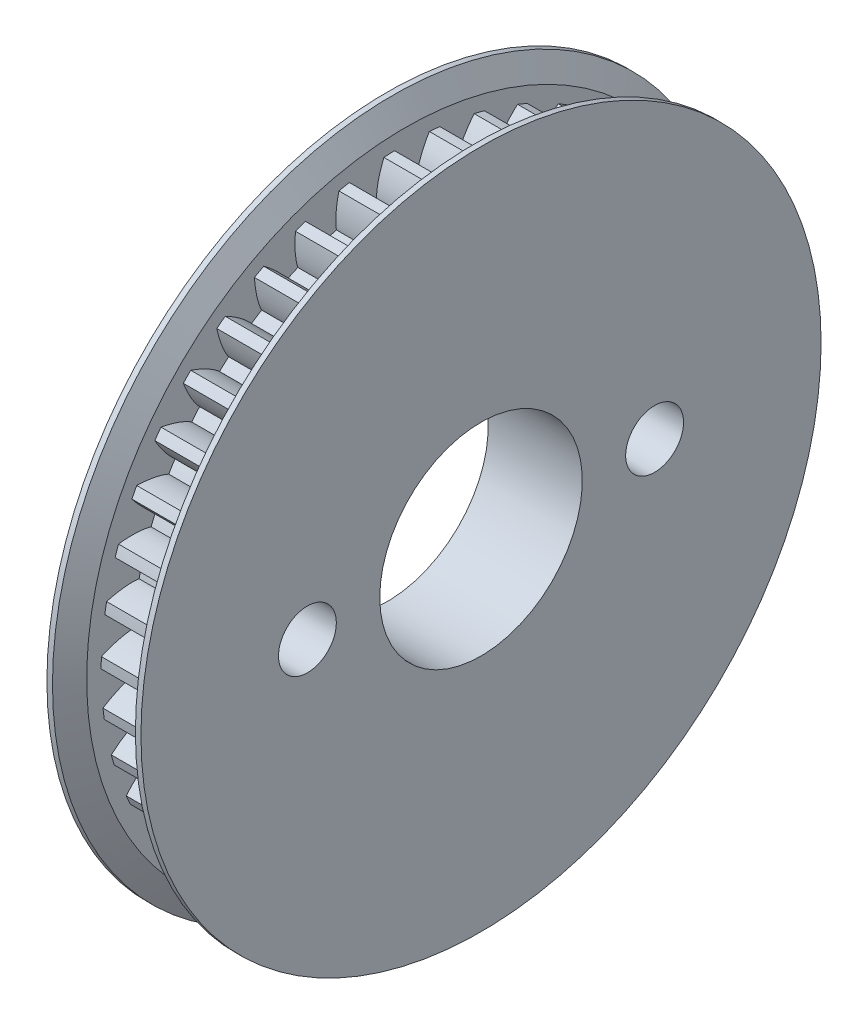
SolidWorks part; units mm, degrees
material "6061-T6 (SS)"
ref_plane "Front Plane" through (0, 0, 0) normal (1, 0, 0) x (0, 1, 0)
ref_plane "Top Plane" through (0, 0, 0) normal (0, 0, 1) x (0, 1, 0)
ref_plane "Right Plane" through (0, 0, 0) normal (0, 1, 0) x (-1, 0, 0)
sketch "Sketch1" plane through (0, 0, 0) normal (1, 0, 0) x (0, 1, 0)
  circle A0 centre (0, 0) radius 21.0085
  circle A1 centre (0, 0) radius 18.8441 construction
  circle A2 centre (0, 0) radius 18.8599 construction
  circle A3 centre (0, 0) radius 20.0535 construction
  dimension "D1" = 42.0169
  dimension "D2" = 37.6883
  dimension "D3" = 37.7197
  dimension "D4" = 40.107
extrude "Boss-Extrude1" add sketch "Sketch1" along normal blind 4
sketch "Sketch3" plane through (4, 0, 0) normal (1, 0, 0) x (0, 1, 0)
  line L0 (0, 0) -> (18.8441, 0) construction
  line L1 (0, 0) -> (20.0513, 0.2989) construction
  line L2 (0, 0) -> (20.0484, -0.4511) construction
  line L3 (20.0484, -0.4511) -> (18.8394, -0.4239)
  line L4 (20.0484, -0.4511) -> (26.0383, -0.5858)
  line L5 (26.0383, 5.6753) -> (26.0383, -0.5858)
  line L6 (18.8441, 0) -> (18.8599, 0)
  line L7 (18.8394, -0.4239) -> (18.8551, -0.4242)
  circle A0 centre (0, 0) radius 20.0535 construction
  circle A1 centre (0, 0) radius 18.8441 construction
  circle A2 centre (0, 0) radius 18.8599 construction
  arc A3 (18.8599, 0) -> (18.8551, -0.4242) centre (0, 0) cw
  spline S0 degree 4 poles (18.8441, 0) (18.8581, 0.0003) (18.8971, 0.002) (18.9708, 0.0089) (19.0905, 0.0253) (19.242, 0.0535) (19.4365, 0.0986) (19.6634, 0.1625) (19.9101, 0.2441) (20.175, 0.3448) (20.436, 0.456) (20.6929, 0.5763) (20.9457, 0.7052) (21.2473, 0.8707) (21.6037, 1.0842) (22.0093, 1.3516) (22.4593, 1.681) (22.901, 2.0358) (23.3282, 2.4114) (23.7378, 2.8006) (24.1355, 3.2108) (24.5122, 3.6264) (24.8835, 4.0701) (25.1799, 4.4449) (25.4486, 4.8104) (25.6694, 5.1179) (25.9451, 5.5285) (26.1166, 5.7943) (26.3702, 6.2065) (26.4595, 6.3635) (26.5307, 6.485) knots 0 0 0 0 0 0.005377 0.015084 0.028532 0.04661 0.064855 0.092111 0.119476 0.146842 0.174209 0.201575 0.228941 0.256307 0.307035 0.361767 0.4165 0.471232 0.525964 0.580697 0.635429 0.690161 0.744894 0.799626 0.826992 0.854358 0.909091 0.954545 1 1 1 1 1 construction
  spline S1 degree 4 poles (18.8441, 0) (18.8581, 0.0003) (18.8971, 0.002) (18.9708, 0.0089) (19.0905, 0.0253) (19.242, 0.0535) (19.4365, 0.0986) (19.6634, 0.1625) (19.9101, 0.2441) (20.175, 0.3448) (20.436, 0.456) (20.6929, 0.5763) (20.9457, 0.7052) (21.2473, 0.8707) (21.6037, 1.0842) (22.0093, 1.3516) (22.4593, 1.681) (22.901, 2.0358) (23.3282, 2.4114) (23.7378, 2.8006) (24.1355, 3.2108) (24.5122, 3.6264) (24.8835, 4.0701) (25.1799, 4.4449) (25.4486, 4.8104) (25.6694, 5.1179) (25.8642, 5.4081) (25.9687, 5.5668) (26.0383, 5.6753) knots 0 0 0 0 0 0.005377 0.015084 0.028532 0.04661 0.064855 0.092111 0.119476 0.146842 0.174209 0.201575 0.228941 0.256307 0.307035 0.361767 0.4165 0.471232 0.525964 0.580697 0.635429 0.690161 0.744894 0.799626 0.826992 0.854358 0.909091 0.909091 0.909091 0.909091 0.909091
  circle M1 centre (0, 0) radius 21.0085
  dimension "D1" = 2.143
extrude "Cut-Extrude1" cut sketch "Sketch3" against normal through all contours S1 L6 A3 L3 L4 M1 region at (4, 20.1257, -0.0464)
mirror "Mirror1" about plane through (0, 0, 0) normal (0, 0.0225, 0.9997) of "Cut-Extrude1"
pattern_circular "CirPattern6" count 42 over 360 about axis through (4, 0, 0) along (-1, 0, 0) of "Cut-Extrude1", "Mirror1"
sketch "Sketch5" plane through (0, 0, 0) normal (0, 1, 0) x (-1, 0, 0)
  line L0 (-15.044, 0) -> (9.7198, 0) construction
  line L1 (-4, 0) -> (-5.25, 0)
  line L2 (-5.25, 0) -> (-5.25, 23.5082)
  line L4 (-4, 22.0082) -> (-4, 0)
  line L5 (0, 0) -> (1.25, 0)
  line L6 (0, 18.8599) -> (0, -18.8599) construction
  line L7 (1.25, 0) -> (1.25, 23.5082)
  line L9 (0, 22.0082) -> (0, 0)
  line L10 (-5.25, 23.5082) -> (-4.866, 23.5082)
  line L11 (-4.866, 23.5082) -> (-4, 22.0082)
  line L12 (0, 22.0082) -> (0.866, 23.5082)
  line L13 (0.866, 23.5082) -> (1.25, 23.5082)
  line L14 (0, 21.0082) -> (-4, 21.0082) construction
  dimension "D1" = 150
  dimension "D2" = 150
  dimension "D3" = 1
  dimension "D4" = 1.5
  dimension "D5" = 1.25
  dimension "D6" = 1.25
revolve "Revolve1" add sketch "Sketch5" angle 360 about L0
sketch "Sketch6" plane through (-1.25, 0, 0) normal (-1, 0, 0) x (0, -1, 0)
  circle A0 centre (0, 0) radius 7
  dimension "D1" = 14
extrude "Cut-Extrude2" cut sketch "Sketch6" against normal through all
sketch "Sketch7" plane through (0, 0, 0) normal (1, 0, 0) x (0, 1, 0)
  line L0 (0, -12) -> (0, 12) construction
  circle A0 centre (0, 12) radius 2
  circle A1 centre (0, -12) radius 2
  point P5 (0, 0)
  dimension "D1" = 4
  dimension "D2" = 24
extrude "Cut-Extrude3" cut sketch "Sketch7" against normal through all both and the other way through all
equation "\"DiametralPitch\"= pi / \"Pitch\""
equation "\"NumberTeeth\"= 42"
equation "\"PressureAngle\"= 20"
equation "\"PitchDiameter\"= \"NumberTeeth\" / \"DiametralPitch\""
equation "\"BaseDiameter\"= \"PitchDiameter\" * cos ( \"PressureAngle\" )"
equation "\"Addendum\"= 1 / \"DiametralPitch\""
equation "\"Dedendum\"= 1.25 / \"DiametralPitch\""
equation "\"AddendumDiameter\"= \"PitchDiameter\" + \"Addendum\" + \"Addendum\""
equation "\"DedendumDiameter\"= \"PitchDiameter\" - \"Dedendum\" - \"Dedendum\""
equation "\"ToothSpacing\"= 360 / ( 4 * \"NumberTeeth\" )"
equation "\"D1@Sketch1\"=\"AddendumDiameter\""
equation "\"D2@Sketch1\"=\"BaseDiameter\""
equation "\"D3@Sketch1\"=\"DedendumDiameter\""
equation "\"D4@Sketch1\"=\"PitchDiameter\""
equation "\"D1@Sketch3\"=\"ToothSpacing\""
equation "\"D1@CirPattern6\"=\"NumberTeeth\""
equation "\"Pitch\"= 3"
